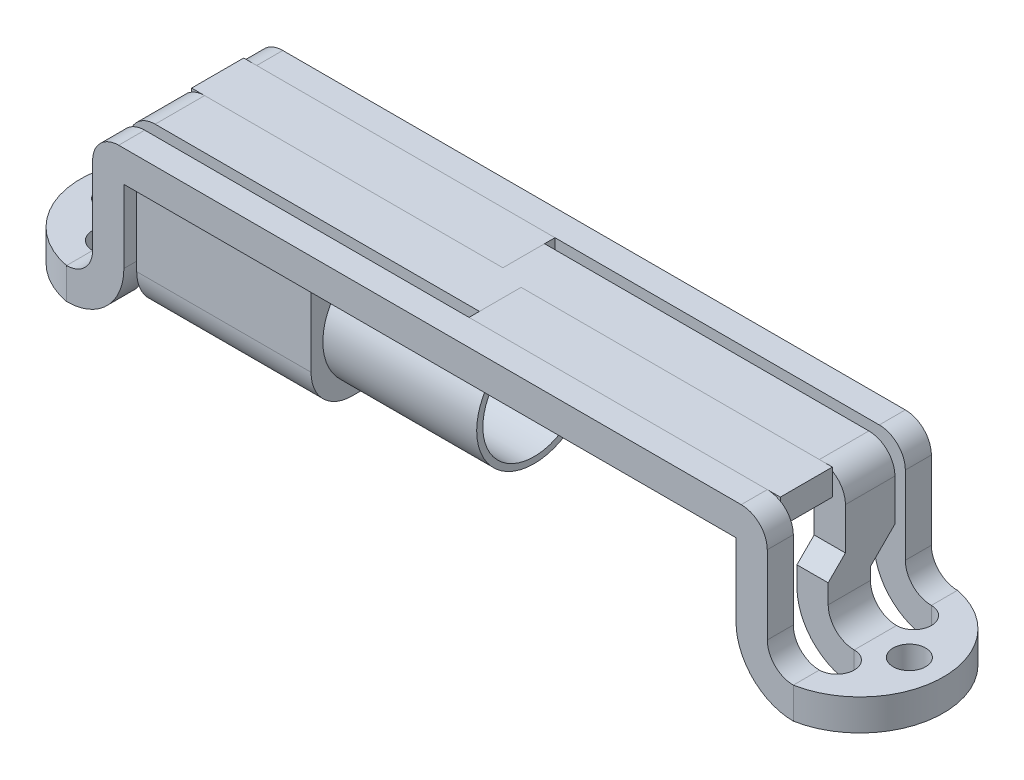
SolidWorks part; units mm, degrees
material "6061-T6 (SS)"
ref_plane "Front Plane" through (0, 0, 0) normal (0, 0, 1) x (1, 0, 0)
ref_plane "Top Plane" through (0, 0, 0) normal (0, 1, 0) x (1, 0, 0)
ref_plane "Right Plane" through (0, 0, 0) normal (1, 0, 0) x (0, 0, -1)
sketch "Sketch1" plane through (0, 0, 0) normal (0, 0, 1) x (1, 0, 0)
  line L0 (-30.353, 0) -> (30.353, 0)
  line L1 (-32.893, -2.54) -> (-32.893, -10.16)
  line L2 (-35.433, -12.7) -> (-42.0688, -12.7)
  line L3 (0, 0) -> (0, -13.9437) construction
  line L4 (35.433, -12.7) -> (42.0688, -12.7)
  line L5 (32.893, -2.54) -> (32.893, -10.16)
  arc A0 (35.433, -12.7) -> (32.893, -10.16) centre (35.433, -10.16) cw
  arc A1 (30.353, 0) -> (32.893, -2.54) centre (30.353, -2.54) cw
  arc A2 (-30.353, 0) -> (-32.893, -2.54) centre (-30.353, -2.54) ccw
  arc A3 (-32.893, -10.16) -> (-35.433, -12.7) centre (-35.433, -10.16) cw
  point P2 (0, 0)
  point P12 (32.893, -12.7)
  point P15 (32.893, 0)
  point P18 (-32.893, 0)
  point P21 (-32.893, -12.7)
  dimension "D4" = 2.54
  dimension "D1" = 84.1375
  dimension "D2" = 65.786
  dimension "D3" = 12.7
extrude "Extrude-Thin1" add sketch "Sketch1" against normal blind 16.002 thin thin type one direction wall 3.048
sketch "Sketch2" plane through (0, 0, 0) normal (0, 1, 0) x (1, 0, 0)
  line L0 (-35.433, 16.002) -> (-42.0688, 16.002)
  line L1 (-42.0688, 16.002) -> (-42.0688, 0)
  line L2 (-42.0688, 0) -> (-35.433, 0)
  line L3 (35.433, 0) -> (42.0688, 0)
  line L4 (42.0688, 0) -> (42.0688, 16.002)
  line L5 (42.0688, 16.002) -> (35.433, 16.002)
  line L6 (-42.0688, 8.001) -> (-35.433, 8.001) construction
  line L7 (-35.433, 16.002) -> (-35.433, 0) construction
  line L8 (-35.433, 8.001) -> (35.433, 8.001) construction
  line L9 (35.433, 16.002) -> (35.433, 0) construction
  line L10 (35.433, 8.001) -> (42.0688, 8.001) construction
  line L11 (-35.433, 16.002) -> (-35.433, 13.462) construction
  line L12 (-35.433, 13.462) -> (-1.27, 13.462)
  line L13 (-1.27, 13.462) -> (0, 13.462)
  line L14 (0, 0) -> (0, 16.002) construction
  line L15 (-30.353, 16.002) -> (30.353, 16.002) construction
  line L16 (0, 13.462) -> (35.433, 13.462)
  line L18 (-32.893, 8.382) -> (-1.27, 8.382)
  line L19 (-1.27, 8.382) -> (-1.27, 12.446)
  line L20 (-35.433, 2.54) -> (-35.433, 4.24) construction
  line L21 (-35.433, 13.462) -> (-35.433, 11.762) construction
  line L22 (-35.433, 10.062) -> (-32.893, 10.062)
  line L23 (-32.893, 16.002) -> (-32.893, 0) construction
  line L24 (-32.893, 10.062) -> (-32.893, 8.382)
  line L25 (-35.433, 5.94) -> (-32.893, 5.94)
  line L26 (0, 2.54) -> (-35.433, 2.54)
  line L27 (-32.893, 3.556) -> (1.27, 3.556)
  line L28 (1.27, 2.54) -> (0, 2.54)
  line L29 (1.27, 7.62) -> (1.27, 3.556)
  line L30 (35.433, 2.54) -> (1.27, 2.54)
  line L31 (32.893, 7.62) -> (1.27, 7.62)
  line L32 (35.433, 13.462) -> (35.433, 11.762) construction
  line L33 (35.433, 2.54) -> (35.433, 4.24) construction
  line L34 (35.433, 10.062) -> (32.893, 10.062)
  line L35 (32.893, 16.002) -> (32.893, 0) construction
  line L36 (32.893, 10.062) -> (32.893, 12.446)
  line L37 (35.433, 5.94) -> (32.893, 5.94)
  line L38 (32.893, 5.94) -> (32.893, 7.62)
  line L39 (-32.893, 5.94) -> (-32.893, 3.556)
  line L40 (32.893, 12.446) -> (-1.27, 12.446)
  arc A0 (-35.433, 16.002) -> (-35.433, 0) centre (-33.9273, 8.001) ccw
  arc A1 (35.433, 16.002) -> (35.433, 0) centre (33.9273, 8.001) cw
  circle A2 centre (-38.7509, 8.001) radius 1.5875
  circle A3 centre (38.7509, 8.001) radius 1.5875
  arc A6 (-35.433, 5.94) -> (-35.433, 2.54) centre (-35.433, 4.24) ccw
  arc A7 (-35.433, 13.462) -> (-35.433, 10.062) centre (-35.433, 11.762) ccw
  arc A10 (35.433, 10.062) -> (35.433, 13.462) centre (35.433, 11.762) ccw
  arc A11 (35.433, 2.54) -> (35.433, 5.94) centre (35.433, 4.24) ccw
  line M4 (30.353, 0) -> (30.353, 16.002)
  line M6 (-30.353, 16.002) -> (-30.353, 0)
  dimension "D1" = 2.54
  dimension "D2" = 1.27
  dimension "D3" = 5.08
extrude "Cut-Extrude1" cut sketch "Sketch2" against normal through all contours A0 L0 L1 | A0 L1 L2 | L18 L12 M6 | L18 L19 L16 L13 L12 M4 M6 | L31 L29 L27 L26 L28 L30 M4 M6 | L31 L30 M4 | A3 | L4 A1 L3 | L5 A1 L4 | L16 M4 | L26 L27 M6 | A2 | L19 L40 L36 L34 A10 L16 L13 L12 A7 L22 L24 L18 region at (-40.3835, 0, -14.1912) region at (-40.3835, 0, -1.8108) region at (40.3835, 0, -1.8108) region at (40.3835, 0, -14.1912) region at (-33.2529, 0, -11.3464) region at (-10.3898, 0, -11.285) region at (-34.3208, 0, -4.0448) region at (10.3898, 0, -4.717) region at (34.3208, 0, -11.9572) region at (33.2529, 0, -4.6556) region at (-38.7509, 0, -8.001) region at (38.7509, 0, -8.001)
sketch "Sketch3" plane through (0, 0, 0) normal (0, 1, 0) x (1, 0, 0)
  line L0 (-32.893, 13.462) -> (-30.353, 13.462) construction
  line L1 (-1.27, 8.382) -> (-31.623, 8.382)
  line L2 (-1.27, 8.382) -> (-1.27, 13.462)
  line L3 (-1.27, 13.462) -> (-31.623, 13.462)
  line L4 (-31.623, 8.382) -> (-31.623, 13.462)
  line L6 (1.27, 7.62) -> (31.623, 7.62)
  line L7 (1.27, 7.62) -> (1.27, 2.54)
  line L8 (1.27, 2.54) -> (31.623, 2.54)
  line L9 (31.623, 7.62) -> (31.623, 2.54)
  line L10 (32.893, 2.54) -> (30.353, 2.54) construction
extrude "Boss-Extrude1" add sketch "Sketch3" against normal blind 2.54 separate body
sketch "Sketch4" plane through (0, 0, 0) normal (0, 1, 0) x (1, 0, 0)
  line L0 (0, 0) -> (0, 16.002) construction
  line L1 (-30.353, 16.002) -> (30.353, 16.002) construction
  line L21 (-32.893, 17.272) -> (-35.5471, 17.272)
  line L22 (-35.5471, -1.27) -> (-32.893, -1.27)
  line L23 (-32.893, -1.27) -> (-30.353, -1.27)
  line L24 (-30.353, -1.27) -> (30.353, -1.27)
  line L25 (30.353, -1.27) -> (32.893, -1.27)
  line L26 (32.893, -1.27) -> (35.5471, -1.27)
  line L27 (35.5471, 17.272) -> (32.893, 17.272)
  line L28 (32.893, 17.272) -> (30.353, 17.272)
  line L29 (-30.353, 17.272) -> (30.353, 17.272)
  line L30 (-30.353, 17.272) -> (-32.893, 17.272)
  line L32 (-43.3388, 8.001) -> (43.3388, 8.001) construction
  arc A4 (-35.5471, 17.272) -> (-35.5471, -1.27) centre (-33.9273, 8.001) ccw
  arc A5 (35.5471, -1.27) -> (35.5471, 17.272) centre (33.9273, 8.001) ccw
sketch "Sketch6" plane through (0, 0, -8.382) normal (0, 0, -1) x (-1, 0, 0)
  line L0 (32.893, -10.16) -> (32.893, -2.54) construction
  line L1 (32.893, -15.1374) -> (32.893, -10.16) construction
  line L2 (29.845, -3.048) -> (29.845, -10.16) construction
  line L3 (32.893, -10.16) -> (32.893, -6.604)
  line L4 (32.893, -15.1374) -> (32.893, -10.16)
  line L5 (29.845, -6.604) -> (29.845, -10.16)
  line L7 (32.893, -10.16) -> (32.893, -6.604) construction
  line L8 (32.893, -6.604) -> (29.845, -6.604)
  arc A0 (29.845, -10.16) -> (32.893, -15.1374) centre (35.433, -10.16) ccw construction
  arc A1 (29.845, -10.16) -> (32.893, -15.1374) centre (35.433, -10.16) ccw
extrude "Boss-Extrude2" add sketch "Sketch6" along normal up to surface (1.68 mm away) up to face at (-34.0224, -13.6055, -10.062)
sketch "Sketch7" plane through (0, 0, -7.62) normal (0, 0, 1) x (1, 0, 0)
  line L0 (32.893, -10.16) -> (32.893, -2.54) construction
  line L1 (32.893, -15.1374) -> (32.893, -10.16) construction
  line L2 (29.845, -3.048) -> (29.845, -10.16) construction
  line L3 (32.893, -10.16) -> (32.893, -6.6)
  line L4 (32.893, -15.1374) -> (32.893, -10.16)
  line L5 (29.845, -6.604) -> (29.845, -10.16)
  line L6 (32.893, -10.16) -> (32.893, -6.6) construction
  line L7 (32.893, -6.6) -> (29.845, -6.604)
  arc A0 (29.845, -10.16) -> (32.893, -15.1374) centre (35.433, -10.16) ccw construction
  arc A1 (29.845, -10.16) -> (32.893, -15.1374) centre (35.433, -10.16) ccw
extrude "Boss-Extrude3" add sketch "Sketch7" along normal up to surface (1.68 mm away) up to face at (34.0224, -13.6055, -5.94)
sketch "Sketch8" plane through (0, 0, -12.446) normal (0, 0, -1) x (-1, 0, 0)
  line L0 (-32.893, -15.1374) -> (-32.893, -2.54) construction
  line L1 (-29.845, -3.048) -> (-29.845, -10.16) construction
  line L2 (-32.893, -15.1374) -> (-32.893, -6.6)
  line L3 (-29.845, -6.604) -> (-29.845, -10.16)
  line L4 (-29.845, -6.604) -> (-32.893, -6.6)
  arc A0 (-32.893, -15.1374) -> (-29.845, -10.16) centre (-35.433, -10.16) ccw construction
  arc A1 (-32.893, -15.1374) -> (-29.845, -10.16) centre (-35.433, -10.16) ccw
extrude "Cut-Extrude2" cut sketch "Sketch8" against normal up to surface (2.384 mm away) up to face at (34.0224, -13.6055, -10.062)
sketch "Sketch9" plane through (0, 0, -3.556) normal (0, 0, 1) x (1, 0, 0)
  line L0 (-32.893, -15.1374) -> (-32.893, -2.54) construction
  line L1 (-29.845, -3.048) -> (-29.845, -10.16) construction
  line L2 (-32.893, -15.1374) -> (-32.893, -6.604)
  line L3 (-29.845, -6.604) -> (-29.845, -10.16)
  line L4 (-32.893, -6.604) -> (-29.845, -6.604)
  arc A0 (-32.893, -15.1374) -> (-29.845, -10.16) centre (-35.433, -10.16) ccw construction
  arc A1 (-32.893, -15.1374) -> (-29.845, -10.16) centre (-35.433, -10.16) ccw
extrude "Cut-Extrude3" cut sketch "Sketch9" against normal up to surface (2.384 mm away) up to face at (-34.0224, -13.6055, -5.94)
chamfer "Chamfer1" distance 1.7 angle 45 2 edges at (-31.369, -6.604, -10.062) (31.369, -6.602, -5.94)
chamfer "Chamfer2" distance 2.38 angle 45 2 edges at (-31.369, -6.604, -5.94) (31.369, -6.602, -10.062)
sketch "Sketch10" plane through (0, -3.048, 0) normal (0, -1, 0) x (1, 0, 0)
  line L0 (-29.845, 0) -> (-29.845, -16.002) construction
  line L1 (-29.845, -1.251) -> (-29.845, -14.751)
  line L2 (-29.845, -1.251) -> (-12.845, -1.251)
  line L3 (-12.845, -1.251) -> (-12.845, -14.751)
  line L4 (-12.845, -14.751) -> (-29.845, -14.751)
  point P7 (-29.845, -8.001)
  dimension "D1" = 13.5
  dimension "D2" = 17
extrude "Boss-Extrude4" add sketch "Sketch10" along normal blind 12
sketch "Sketch11" plane through (-12.845, 0, 0) normal (1, 0, 0) x (0, 0, -1)
  line L0 (14.751, -15.048) -> (1.251, -3.048) construction
  circle A0 centre (8.001, -9.048) radius 5.6
  circle A1 centre (8.001, -9.048) radius 5
extrude "Boss-Extrude5" add sketch "Sketch11" along normal blind 15
fillet "Fillet1" radius 4 2 edges at (-21.345, -15.048, -1.251) (-21.345, -15.048, -14.751)
